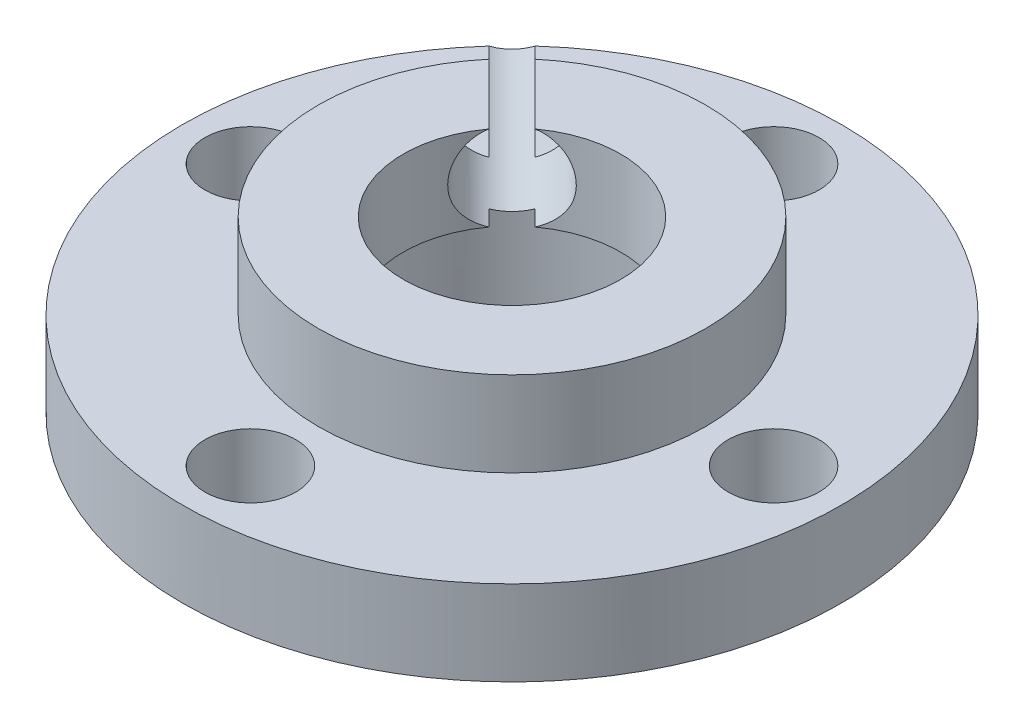
SolidWorks part; units mm, degrees
ref_plane "Front Plane" through (0, 0, 0) normal (0, 0, 1) x (1, 0, 0)
ref_plane "Top Plane" through (0, 0, 0) normal (0, 1, 0) x (1, 0, 0)
ref_plane "Right Plane" through (0, 0, 0) normal (1, 0, 0) x (0, 0, -1)
sketch "Sketch1" plane through (0, 0, 0) normal (0, 1, 0) x (1, 0, 0)
  circle A0 centre (0, 0) radius 4.064
  circle A1 centre (0, 0) radius 7.239
  circle A2 centre (0, 0) radius 12.319
  dimension "D1" = 8.128
  dimension "D2" = 3.175
  dimension "D3" = 5.08
extrude "Boss-Extrude1" add sketch "Sketch1" along normal blind 6.35 contours A1 A0 region at (-7.0343, 0, 0)
extrude "Boss-Extrude2" add sketch "Sketch1<3>" along normal blind 3.175 contours A2 A1 region at (-11.9706, 0, 0)
sketch "Sketch1<3>" plane through (0, 0, 0) normal (0, 1, 0) x (1, 0, 0) same geometry as "Sketch1"
sketch "Sketch2" plane through (0, 3.175, 0) normal (0, 1, 0) x (1, 0, 0)
  line L0 (0, 12.319) -> (0, 7.239) construction
  circle A0 centre (0, 9.779) radius 1.7
  circle A1 centre (9.779, 0) radius 1.7
  circle A2 centre (0, -9.779) radius 1.7
  circle A3 centre (-9.779, 0) radius 1.7
  circle A4 centre (0, 0) radius 12.319 construction
  circle A5 centre (0, 0) radius 7.239 construction
  point P4 (0, 9.779)
  point P11 (0, 0)
  dimension "D1" = 3.4
  dimension "D2" = 4
extrude "Cut-Extrude1" cut sketch "Sketch2" against normal blind 3.175
ref_axis "Axis1" through (0, 0, -9.779) along (0, 1, 0)
ref_axis "Axis2" through (-9.779, 0, 0) along (0, 1, 0)
ref_plane "Plane1" through (-4.8895, 0, -4.8895) normal (-0.7071, 0, -0.7071) x (-0.7071, 0, 0.7071)
sketch "Sketch7" plane through (0, 0, 0) normal (0, -1, 0) x (1, 0, 0)
  circle A0 centre (0, 0) radius 4.8895
  dimension "D1" = 9.779
extrude "Cut-Extrude3" cut sketch "Sketch7" against normal blind 3.175
sketch "Sketch5" plane through (-4.8895, 0, -4.8895) normal (-0.7071, 0, -0.7071) x (-0.7071, 0, 0.7071)
  line L0 (0, 6.35) -> (0, 3.175) construction
  line L1 (7.239, 6.35) -> (-7.239, 6.35) construction
  line L2 (12.319, 3.175) -> (-12.319, 3.175) construction
  circle A0 centre (0, 4.7625) radius 1.7
  point P10 (0, 4.7625)
  dimension "D1" = 3.4
extrude "Cut-Extrude2" cut sketch "Sketch5" against normal up to next and the other way up to next
sketch "Sketch6" plane through (0, 0, 0) normal (0, 1, 0) x (1, 0, 0)
  circle A0 centre (0, 0) radius 9.779 construction
